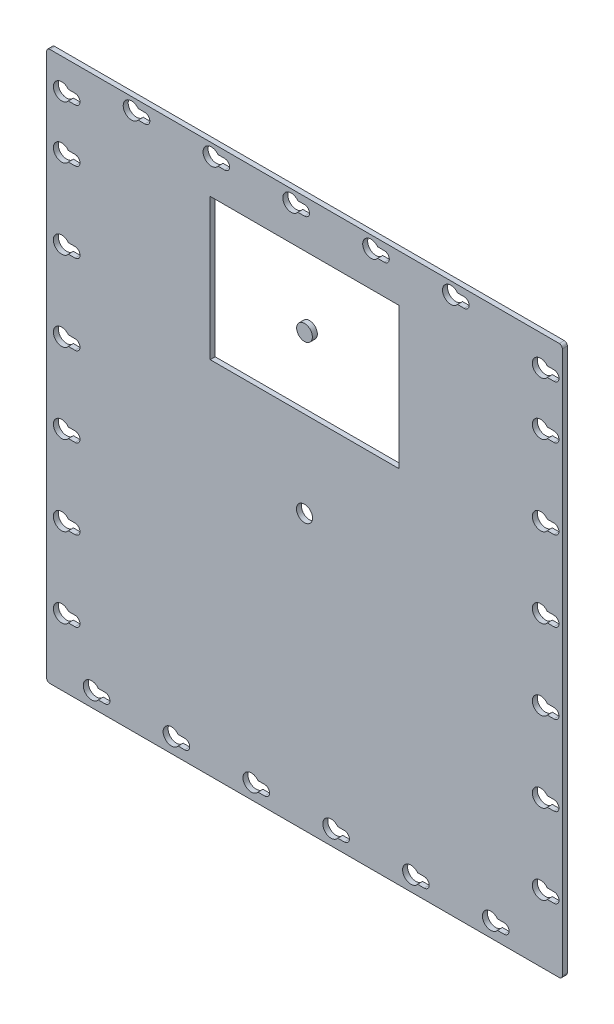
SolidWorks part; units mm, degrees
material "6061 Alloy"
ref_plane "Front Plane" through (0, 0, 0) normal (0, 0, 1) x (1, 0, 0)
ref_plane "Top Plane" through (0, 0, 0) normal (0, 1, 0) x (1, 0, 0)
ref_plane "Right Plane" through (0, 0, 0) normal (1, 0, 0) x (0, 0, -1)
sketch "Sketch1" plane through (0, 0, 0) normal (0, 0, 1) x (1, 0, 0)
  line L0 (0, 0) -> (0, -174.745)
  line L3 (0, -174.745) -> (165.1, -174.745)
  line L5 (0, 0) -> (165.1, 0)
  line L6 (165.1, -174.745) -> (165.1, 0)
  line L7 (82.55, 0) -> (82.55, -174.745) construction
  line L8 (31.75, -2.2625) -> (29.6344, -2.2625)
  line L9 (31.75, -5.4375) -> (29.6344, -5.4375)
  line L10 (9.525, -24.9325) -> (7.4094, -24.9325)
  line L11 (9.525, -28.1075) -> (7.4094, -28.1075)
  line L12 (161.925, -24.9325) -> (159.8094, -24.9325)
  line L13 (161.925, -28.1075) -> (159.8094, -28.1075)
  line L14 (57.15, -2.2625) -> (55.0344, -2.2625)
  line L15 (57.15, -5.4375) -> (55.0344, -5.4375)
  line L16 (82.55, -2.2625) -> (80.4344, -2.2625)
  line L17 (82.55, -5.4375) -> (80.4344, -5.4375)
  line L18 (107.95, -2.2625) -> (105.8344, -2.2625)
  line L19 (107.95, -5.4375) -> (105.8344, -5.4375)
  line L20 (133.35, -2.2625) -> (131.2344, -2.2625)
  line L21 (133.35, -5.4375) -> (131.2344, -5.4375)
  line L22 (9.525, -50.3325) -> (7.4094, -50.3325)
  line L23 (9.525, -53.5075) -> (7.4094, -53.5075)
  line L24 (161.925, -50.3325) -> (159.8094, -50.3325)
  line L25 (161.925, -53.5075) -> (159.8094, -53.5075)
  line L26 (9.525, -75.7325) -> (7.4094, -75.7325)
  line L27 (9.525, -78.9075) -> (7.4094, -78.9075)
  line L28 (161.925, -75.7325) -> (159.8094, -75.7325)
  line L29 (161.925, -78.9075) -> (159.8094, -78.9075)
  line L30 (9.525, -101.1325) -> (7.4094, -101.1325)
  line L31 (9.525, -104.3075) -> (7.4094, -104.3075)
  line L32 (161.925, -101.1325) -> (159.8094, -101.1325)
  line L33 (161.925, -104.3075) -> (159.8094, -104.3075)
  line L34 (9.525, -126.5325) -> (7.4094, -126.5325)
  line L35 (9.525, -129.7075) -> (7.4094, -129.7075)
  line L36 (161.925, -126.5325) -> (159.8094, -126.5325)
  line L37 (161.925, -129.7075) -> (159.8094, -129.7075)
  line L38 (9.525, -151.9325) -> (7.4094, -151.9325)
  line L39 (9.525, -155.1075) -> (7.4094, -155.1075)
  line L40 (161.925, -151.9325) -> (159.8094, -151.9325)
  line L41 (161.925, -155.1075) -> (159.8094, -155.1075)
  line L42 (19.05, -168.395) -> (16.9344, -168.395)
  line L43 (19.05, -171.57) -> (16.9344, -171.57)
  line L44 (44.45, -168.395) -> (42.3344, -168.395)
  line L45 (44.45, -171.57) -> (42.3344, -171.57)
  line L46 (69.85, -168.395) -> (67.7344, -168.395)
  line L47 (69.85, -171.57) -> (67.7344, -171.57)
  line L48 (95.25, -168.395) -> (93.1344, -168.395)
  line L49 (95.25, -171.57) -> (93.1344, -171.57)
  line L50 (120.65, -168.395) -> (118.5344, -168.395)
  line L51 (120.65, -171.57) -> (118.5344, -171.57)
  line L52 (146.05, -168.395) -> (143.9344, -168.395)
  line L53 (146.05, -171.57) -> (143.9344, -171.57)
  line L54 (0.5, 0) -> (0.5, -174.745)
  line L55 (164.6, -174.745) -> (164.6, 0)
  line L56 (0.5, -174.745) -> (164.6, -174.745)
  line L57 (9.525, -8.1) -> (7.4094, -8.1)
  line L58 (9.525, -11.275) -> (7.4094, -11.275)
  line L59 (161.925, -8.1) -> (159.8094, -8.1)
  line L60 (161.925, -11.275) -> (159.8094, -11.275)
  circle A41 centre (9.525, -153.52) radius 1.5875
  circle A42 centre (19.05, -169.9825) radius 1.5875
  circle A43 centre (9.525, -128.12) radius 1.5875
  circle A44 centre (9.525, -102.72) radius 1.5875
  circle A45 centre (9.525, -77.32) radius 1.5875
  circle A46 centre (9.525, -51.92) radius 1.5875
  circle A47 centre (9.525, -26.52) radius 1.5875
  circle A49 centre (44.45, -169.9825) radius 1.5875
  circle A50 centre (69.85, -169.9825) radius 1.5875
  circle A51 centre (95.25, -169.9825) radius 1.5875
  circle A52 centre (120.65, -169.9825) radius 1.5875
  circle A68 centre (146.05, -169.9825) radius 1.5875
  circle A69 centre (107.95, -3.85) radius 1.5875
  circle A70 centre (82.55, -3.85) radius 1.5875
  circle A71 centre (57.15, -3.85) radius 1.5875
  circle A72 centre (9.525, -1.12) radius 1.5875 [skipped]
  circle A73 centre (133.35, -3.85) radius 1.5875
  circle A74 centre (31.75, -3.85) radius 1.5875
  circle A75 centre (161.925, -26.52) radius 1.5875
  circle A76 centre (161.925, -51.92) radius 1.5875
  circle A77 centre (161.925, -77.32) radius 1.5875
  circle A78 centre (161.925, -102.72) radius 1.5875
  circle A79 centre (161.925, -128.12) radius 1.5875
  circle A80 centre (161.925, -153.52) radius 1.5875
  circle A81 centre (27.5125, -3.85) radius 2.65
  circle A83 centre (5.2875, -26.52) radius 2.65
  circle A84 centre (157.6875, -26.52) radius 2.65
  circle A85 centre (52.9125, -3.85) radius 2.65
  circle A86 centre (78.3125, -3.85) radius 2.65
  circle A87 centre (103.7125, -3.85) radius 2.65
  circle A88 centre (129.1125, -3.85) radius 2.65
  circle A89 centre (5.2875, -51.92) radius 2.65
  circle A90 centre (157.6875, -51.92) radius 2.65
  circle A91 centre (5.2875, -77.32) radius 2.65
  circle A92 centre (157.6875, -77.32) radius 2.65
  circle A93 centre (5.2875, -102.72) radius 2.65
  circle A94 centre (157.6875, -102.72) radius 2.65
  circle A95 centre (5.2875, -128.12) radius 2.65
  circle A96 centre (157.6875, -128.12) radius 2.65
  circle A97 centre (5.2875, -153.52) radius 2.65
  circle A98 centre (157.6875, -153.52) radius 2.65
  circle A99 centre (14.8125, -169.9825) radius 2.65
  circle A100 centre (40.2125, -169.9825) radius 2.65
  circle A101 centre (65.6125, -169.9825) radius 2.65
  circle A102 centre (91.0125, -169.9825) radius 2.65
  circle A103 centre (116.4125, -169.9825) radius 2.65
  circle A104 centre (141.8125, -169.9825) radius 2.65
  circle A105 centre (82.55, -87.3725) radius 2.5527
  circle A107 centre (9.525, -9.6875) radius 1.5875
  circle A108 centre (5.2875, -9.6875) radius 2.65
  circle A109 centre (161.925, -9.6875) radius 1.5875
  circle A110 centre (157.6875, -9.6875) radius 2.65
  dimension "D3" = 3.175
  dimension "D8" = 3.175
  dimension "D21" = 5.3
  dimension "D31" = 5.1054
  dimension "D33" = 5.3
  dimension "D1" = 165.1
  dimension "D2" = 174.745
  dimension "D5" = 9.525
  dimension "D4" = 21.225
  dimension "D6" = 19.05
  dimension "D7" = 4.7625
  dimension "D9" = 25.4
  dimension "D10" = 25.4
  dimension "D15" = 25.4
  dimension "D12" = 3.85
  dimension "D13" = 31.75
  dimension "D17" = 31.75
  dimension "D18" = 3.175
  dimension "D20" = 25.4
  dimension "D23" = 25.4
  dimension "D25" = 25.4
  dimension "D27" = 25.4
  dimension "D28" = 0.5
  dimension "D29" = 0.5
  dimension "D30" = 87.3725
  dimension "D34" = 16.8325
  dimension "D35" = 5.8375
  dimension "D11" = 7
  dimension "D14" = 5
  dimension "D16" = 5
  dimension "D19" = 6
  dimension "D22" = 5
  dimension "D24" = 6
  dimension "D26" = 6
extrude "Boss-Extrude1" add sketch "Sketch1" along normal blind 1.5875 contours L7 L5 L0 L3 A50 A41 A42 A43 A44 A45 A46 A47 A73 A49 | L5 L7 A70 A105 L56 L55 A84 L12 A75 L13 A87 L18 A69 L19 A88 L20 A73 L21 A90 L24 A76 L25 A92 L28 A77 L29 A94 L32 A78 L33 A96 L36 A79 L37 A98 L40 A80 L41 A102 L48
fillet "Fillet1" radius 1 4 edges at (164.6, 0, 0.7937) (164.6, -174.745, 0.7937) (0.5, -174.745, 0.7937) (0.5, 0, 0.7937)
sketch "Sketch2" plane through (0, 0, 1.5875) normal (0, 0, 1) x (1, 0, 0)
  line L0 (1.5, 0) -> (163.6, 0) construction
  line L1 (52.55, -15) -> (112.55, -15)
  line L2 (52.55, -15) -> (52.55, -60)
  line L3 (52.55, -60) -> (112.55, -60)
  line L4 (112.55, -15) -> (112.55, -60)
  circle A0 centre (82.55, -37.5) radius 2.5
  point P6 (82.55, 0)
  point P7 (82.55, -15)
  point P10 (0, 0)
  point P11 (112.55, -37.5)
  dimension "D4" = 5
  dimension "D1" = 45
  dimension "D2" = 60
  dimension "D3" = 15
extrude "Cut-Extrude1" cut sketch "Sketch2" against normal blind 10
equation "\"D8@Sketch1\"=\"D3@Sketch1\""
equation "\"D29@Sketch1\"=\"D28@Sketch1\""
equation "\"D30@Sketch1\"=\"D2@Sketch1\"/2"
equation "\"D2@Sketch2\"=\"D1@Sketch2\"*(4/3)"
